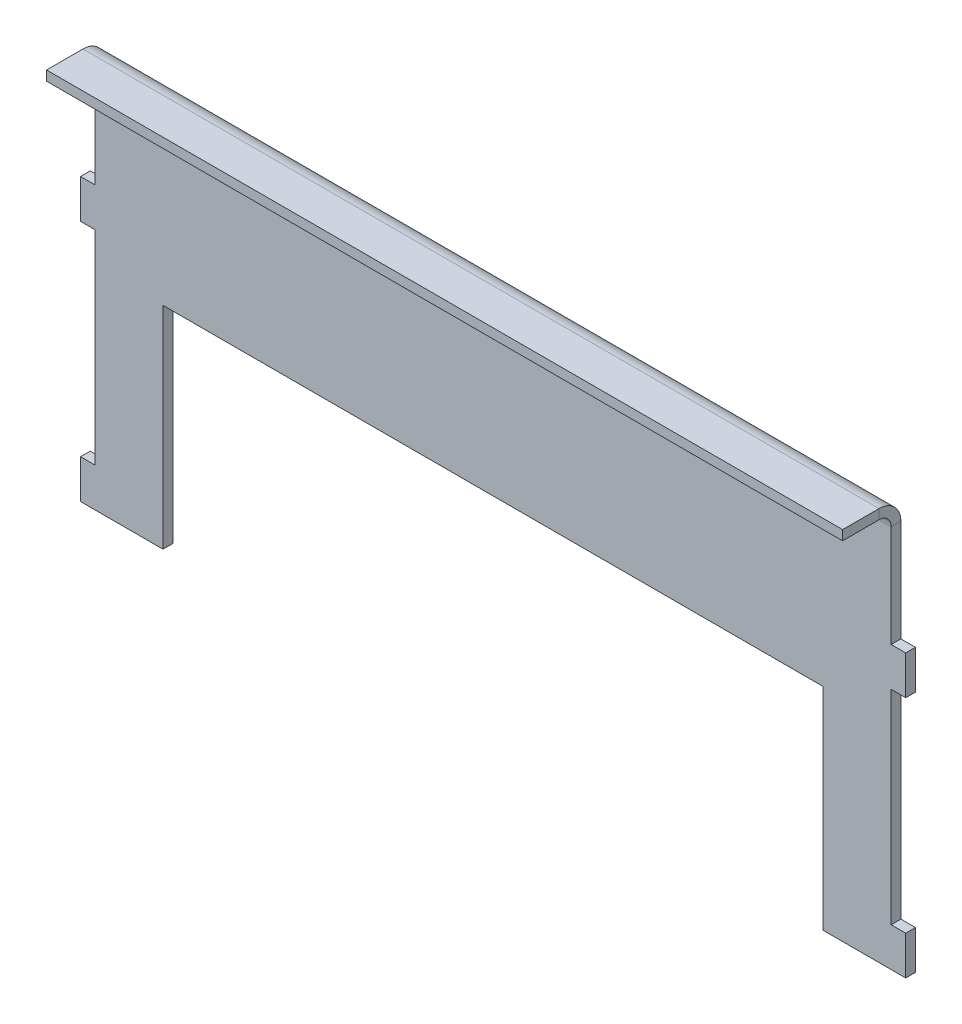
SolidWorks part; units mm, degrees
note: The reader was unsure of these and kept them because the rebuilt part matched: thickness of "Base-Flange1", "Edge-Flange1", "Sheet-Metal28", "Sheet-Metal30"; flange length of "Edge-Flange1".
material "Plain Carbon Steel"
ref_plane "Front" through (0, 0, 0) normal (0, 0, 1) x (1, 0, 0)
ref_plane "Top" through (0, 0, 0) normal (0, 1, 0) x (1, 0, 0)
ref_plane "Right" through (0, 0, 0) normal (1, 0, 0) x (0, 0, -1)
sketch "Sketch1" plane through (0, 0, 0) normal (0, 0, 1) x (1, 0, 0)
  line L0 (-260.35, 127) -> (260.35, 127)
  line L6 (-260.35, 127) -> (-260.35, 46.0375)
  line L24 (-215.9, 0) -> (-215.9, -138.1125)
  line L25 (215.9, 0) -> (215.9, -138.1125)
  line L26 (-269.875, -138.1125) -> (-215.9, -138.1125)
  line L27 (-260.35, 20.6375) -> (-260.35, -112.7125)
  line L28 (-260.35, 46.0375) -> (-269.875, 46.0375)
  line L30 (-260.35, 20.6375) -> (-269.875, 20.6375)
  line L31 (-269.875, 46.0375) -> (-269.875, 20.6375)
  line L32 (-269.875, -138.1125) -> (-269.875, -112.7125)
  line L33 (-260.35, -112.7125) -> (-269.875, -112.7125)
  line L36 (-19.05, -138.1125) -> (-215.9, -138.1125) construction
  line L37 (0, -149.6219) -> (0, -52.0412) construction
  line L38 (19.05, -138.1125) -> (215.9, -138.1125) construction
  line L39 (269.875, -138.1125) -> (215.9, -138.1125)
  line L45 (260.35, -112.7125) -> (269.875, -112.7125)
  line L46 (269.875, -138.1125) -> (269.875, -112.7125)
  line L47 (269.875, 46.0375) -> (269.875, 20.6375)
  line L48 (260.35, 20.6375) -> (269.875, 20.6375)
  line L49 (260.35, 46.0375) -> (269.875, 46.0375)
  line L50 (260.35, 20.6375) -> (260.35, -112.7125)
  line L53 (260.35, 127) -> (260.35, 46.0375)
  line L56 (-215.9, 0) -> (215.9, 0)
  point P0 (0, 0)
  point P3 (0, 0)
  point P41 (0, 0)
  dimension "D6" = 25.4
  dimension "D8" = 9.525
  dimension "D2" = 25.4
  dimension "D3" = 80.9625
  dimension "D4" = 53.975
  dimension "D5" = 265.1125
  dimension "D9" = 260.35
  dimension "D7" = 127
  dimension "D10" = 431.8
base flange "Base-Flange1" sketch "Sketch1" thickness 6.35 reverse thickness direction no parameters "D1"=7.9502
edge flange "Edge-Flange1" sketch "Sketch7" flange angle 90 flange length 38.1 flange position material inside bend radius 7.9502 thickness 6.35 relief rectangular parameters "D6"=10
bend "EdgeBend1" bend radius 7.9502 bend angle 90 parameters "D5"=1
sketch "Sketch7" plane through (0, 127, 0) normal (0, -1, 0) x (1, 0, 0)
  line L2 (-260.35, 0) -> (-260.35, 31.75)
  line L3 (-260.35, 31.75) -> (260.35, 31.75)
  line L4 (260.35, 31.75) -> (260.35, 0)
  line L5 (260.35, 0) -> (-260.35, 0) construction
  line L6 (260.35, 0) -> (-260.35, 0)
sketch "Bend-Lines1" [suppressed] plane through (0, 0, 0) normal (0, 1, 0) x (1, 0, 0)
sketch "Bounding-Box1" [suppressed] plane through (0, 0, 0) normal (0, 1, 0) x (1, 0, 0)
sheet metal parameters "Sheet-Metal28" thickness 6.35 parameters "D1"=3.7592, "D7"=3.0226
flat pattern "Flat-Pattern28" [suppressed]
sketch "Bend-Lines2" plane through (0, 0, 0) normal (0, 1, 0) x (1, 0, 0)
sketch3d "Bounding-Box2" [suppressed]
  line L0 (-269.875, -106.3625, 0) -> (269.875, -106.3625, 0) construction
  line L1 (-269.875, 139.7, 0) -> (269.875, 139.7, 0) construction
  line L2 (-269.875, -106.3625, 0) -> (-269.875, 139.7, 0) construction
  line L3 (269.875, -106.3625, 0) -> (269.875, 139.7, 0) construction
sheet metal parameters "Sheet-Metal30" thickness 6.35 parameters "D1"=3.7592, "D7"=3.0226
flat pattern "Flat-Pattern28"
sketch "Bend-Lines2" plane through (0, 0, 0) normal (0, 0, 1) x (1, 0, 0)
  line L2 (260.35, 121.4375) -> (-260.35, 121.4375) construction
  line L3 (260.35, 121.4375) -> (-260.35, 121.4375) construction
sketch3d "Bounding-Box2" [suppressed]
  line L0 (-269.875, -138.1125, 0) -> (269.875, -138.1125, 0) construction
  line L1 (-269.875, 153.975, 0) -> (269.875, 153.975, 0) construction
  line L2 (-269.875, -138.1125, 0) -> (-269.875, 153.975, 0) construction
  line L3 (269.875, -138.1125, 0) -> (269.875, 153.975, 0) construction
bend of the flat pattern "Flatten-<EdgeBend1>1"
equation "\"Total Cutting Length\"= \"Cutting Length-Outer\" + \"Cutting Length-Inner\""
equation "\"Amount in ft^2\"= \"Bounding Box Area-Blank\" / 144"
